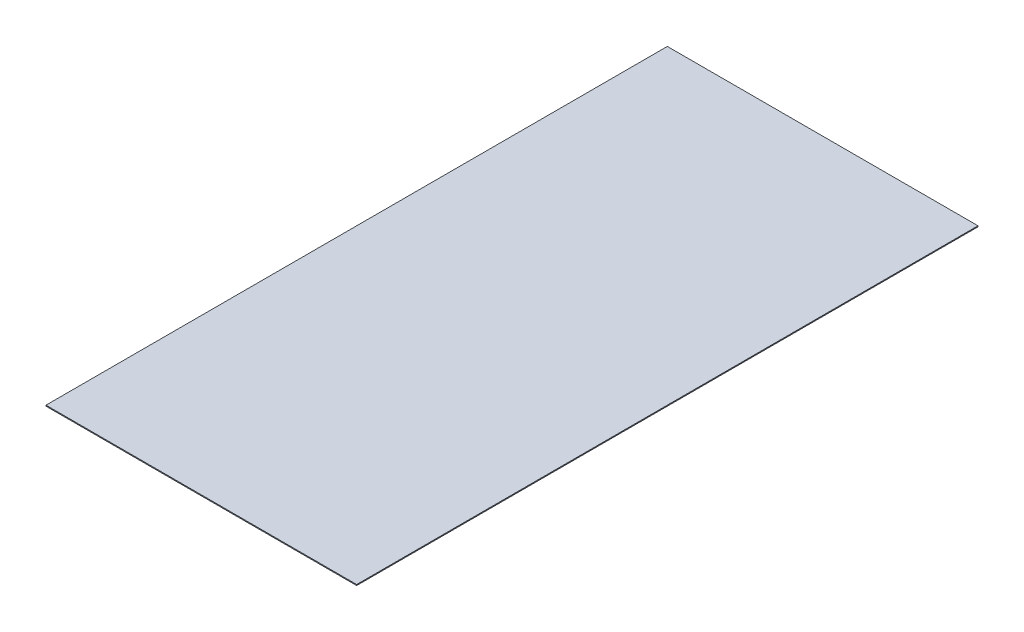
SolidWorks part; units mm, degrees
ref_plane "Front Plane" through (0, 0, 0) normal (0, 0, 1) x (1, 0, 0)
ref_plane "Top Plane" through (0, 0, 0) normal (0, 1, 0) x (1, 0, 0)
ref_plane "Right Plane" through (0, 0, 0) normal (1, 0, 0) x (0, 0, -1)
sketch "Sketch1" plane through (0, 0, 0) normal (0, 1, 0) x (1, 0, 0)
  line L1 (-500, -1000) -> (500, -1000)
  line L2 (-500, -1000) -> (-500, 1000)
  line L3 (-500, 1000) -> (500, 1000)
  line L4 (500, -1000) -> (500, 1000)
  line L5 (-500, -1000) -> (500, 1000) construction
  line L6 (-500, 1000) -> (500, -1000) construction
  point P0 (0, 0)
  dimension "D1" = 1000
  dimension "D2" = 2000
extrude "Boss-Extrude1" add sketch "Sketch1" along normal blind 3
